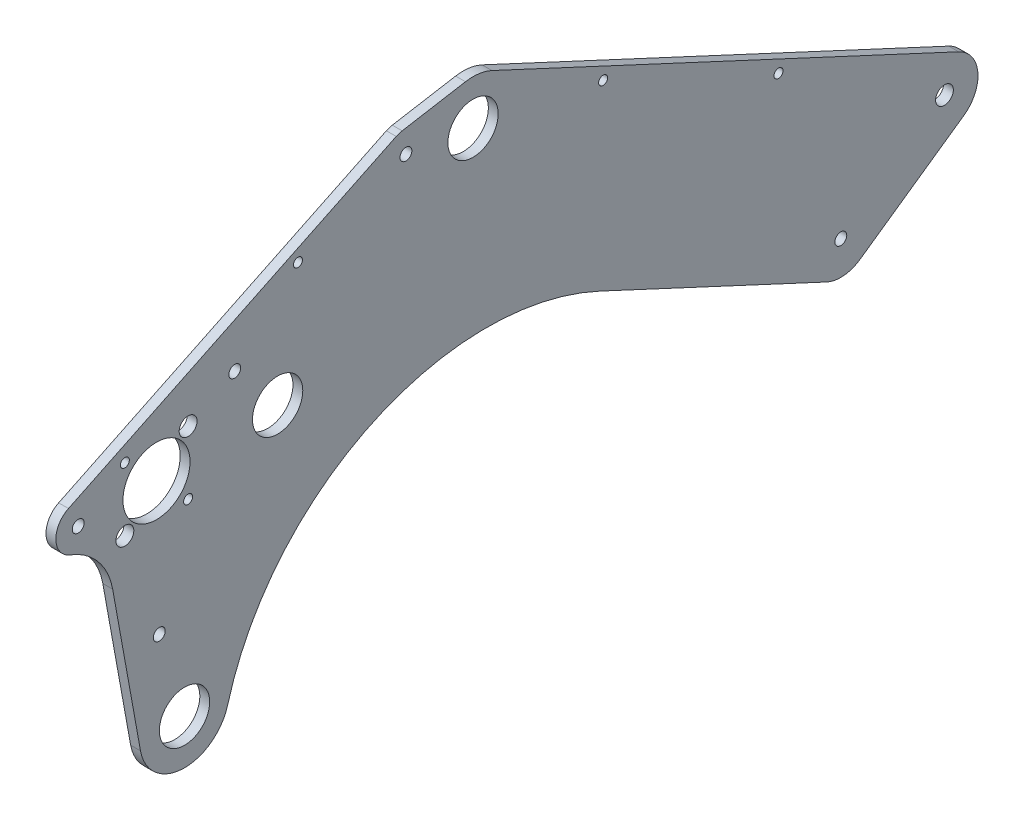
SolidWorks part; units mm, degrees
material "Acrylic (Medium-high impact)"
ref_plane "Front" through (0, 0, 0) normal (0, 0, 1) x (1, 0, 0)
ref_plane "Top" through (0, 0, 0) normal (0, 1, 0) x (1, 0, 0)
ref_plane "Right" through (0, 0, 0) normal (1, 0, 0) x (0, 0, -1)
sketch "Sketch1" plane through (0, 0, 0) normal (1, 0, 0) x (0, 0, -1)
  line L0 (-128.5875, -88.9) -> (-128.5875, -215.9)
  line L1 (-128.5875, -215.9) -> (-179.3875, -215.9)
  line L2 (-211.1375, -184.15) -> (-211.1375, -120.65)
  line L3 (-179.3875, -88.9) -> (-128.5875, -88.9)
  line L4 (-28.6872, -279.4) -> (-968.3377, -279.4) construction
  line L5 (-433.3875, -184.15) -> (-433.3875, -120.65) construction
  line L6 (-120.65, -76.2) -> (-95.25, -76.2)
  line L7 (-120.65, -76.2) -> (-120.65, -101.6)
  line L8 (-120.65, -101.6) -> (-95.25, -101.6)
  line L9 (-95.25, -76.2) -> (-95.25, -101.6)
  line L10 (-179.3875, 133.35) -> (-128.5875, 133.35) construction
  line L11 (-431.4942, -89.6952) -> (-179.3875, -120.65) construction
  line L12 (-378.637, 36.8798) -> (-179.3875, -120.65) construction
  line L13 (-267.6718, 117.5136) -> (-179.3875, -120.65) construction
  line L14 (-449.9497, -81.9883) -> (-397.0925, 44.5867)
  line L15 (-360.1816, 29.1728) -> (-413.0388, -97.4021)
  line L16 (-390.394, 53.0592) -> (-279.4287, 133.693)
  line L17 (-128.5875, -88.9) -> (-128.5875, 338.048) construction
  line L18 (-255.9148, 101.3341) -> (-366.8801, 20.7003)
  line L19 (-534.9875, 270.2474) -> (-534.9875, -123.3484) construction
  line L20 (-427.5738, 36.5062) -> (-411.6579, -87.1419)
  line L21 (-451.3306, -92.2485) -> (-467.2465, 31.3995)
  circle A0 centre (0, 0) radius 5.0419
  circle A1 centre (-431.4942, -89.6952) radius 11.557
  circle A2 centre (-378.637, 36.8798) radius 11.557
  circle A3 centre (-267.6718, 117.5136) radius 11.557
  arc A4 (-179.3875, -215.9) -> (-211.1375, -184.15) centre (-179.3875, -184.15) cw
  arc A5 (-211.1375, -120.65) -> (-179.3875, -88.9) centre (-179.3875, -120.65) cw
  circle A6 centre (-327.5258, -152.4) radius 120.65
  arc A7 (-433.3875, -120.65) -> (-179.3875, 133.35) centre (-179.3875, -120.65) cw construction
  circle A12 centre (-447.4102, 33.9528) radius 31.75
  arc A15 (-413.0388, -97.4021) -> (-449.9497, -81.9883) centre (-431.4942, -89.6952) cw
  arc A16 (-397.0925, 44.5867) -> (-360.1816, 29.1728) centre (-378.637, 36.8798) cw
  arc A17 (-366.8801, 20.7003) -> (-390.394, 53.0592) centre (-378.637, 36.8798) cw
  arc A18 (-279.4287, 133.693) -> (-255.9148, 101.3341) centre (-267.6718, 117.5136) cw
  arc A19 (-467.2465, 31.3995) -> (-427.5738, 36.5062) centre (-447.4102, 33.9528) cw
  arc A20 (-411.6579, -87.1419) -> (-451.3306, -92.2485) centre (-431.4942, -89.6952) cw
  point P45 (0, 0)
  point P46 (-451.0348, 27.3515)
  point P51 (0, 0)
  circle B0 centre (-267.6718, 117.5136) radius 20
  circle B1 centre (-378.637, 36.8798) radius 20
  circle B2 centre (-431.4942, -89.6952) radius 20
  circle B3 centre (-447.4102, 33.9528) radius 20
  dimension "D1" = 10.0838
  dimension "D2" = 23.114
  dimension "D4" = 31.75
  dimension "D10" = 241.3
  dimension "D19" = 63.5
  dimension "D26" = 89.6952
  dimension "D27" = 431.4942
  dimension "D3" = 127
  dimension "D5" = 82.55
  dimension "D6" = 190.5
  dimension "D7" = 25.4
  dimension "D8" = 7.9375
  dimension "D9" = 203.2
  dimension "D12" = 120.65
  dimension "D13" = 76.2
  dimension "D14" = 31.33
  dimension "D15" = 31.33
  dimension "D16" = 7
  dimension "D24" = 406.4
  dimension "D21" = 30
  dimension "D11" = 222.25
sketch_block_instance "Block1-1"
sketch_block "Block1" parameters "D1"=40
sketch_block_instance "Block2-1"
sketch_block "Block2"
sketch_block_instance "Block3-1"
sketch_block "Block3"
sketch_block_instance "Block4-1"
sketch_block "Block4" parameters "D1"=40
other "Belt1"
other "Belt2"
other "Belt4"
sketch "Sketch3" plane through (0, 0, 0) normal (1, 0, 0) x (0, 0, -1)
  line L0 (-431.4942, -89.6952) -> (0, 0) construction
  line L1 (0, 0) -> (-58.8496, -41.2069) construction
  line L2 (0, 0) -> (-89.6952, 431.4942) construction
  line L3 (0, 0) -> (-41.2069, 58.8496) construction
  line L4 (-58.8496, -41.2069) -> (-64.6229, -13.4332) construction
  line L5 (-41.2069, 58.8496) -> (-13.4332, 64.6229) construction
  line L6 (-41.2069, 58.8496) -> (-58.8496, -41.2069)
  line L7 (2.2602, 305.3637) -> (-41.2069, 58.8496)
  line L8 (0, 0) -> (117.5136, 267.6718) construction
  line L9 (0, 0) -> (-267.6718, 117.5136) construction
  line L10 (-267.6718, 117.5136) -> (-233.1688, -48.4691) construction
  line L11 (117.5136, 267.6718) -> (-48.4691, 233.1688) construction
  circle A0 centre (-89.6952, 431.4942) radius 25.4
  dimension "D1" = 50.8
  dimension "D2" = 90
  dimension "D3" = 101.6
  dimension "D4" = 250.317
  dimension "D5" = 80
sketch "Sketch2" plane through (0, 0, 0) normal (1, 0, 0) x (0, 0, -1)
  line L0 (-456.4885, -94.2169) -> (-472.3043, -6.7931)
  line L1 (-497.3852, 45.388) -> (-311.2968, 135.2988)
  line L2 (-431.4942, -89.6952) -> (-431.4942, 0) construction
  line L4 (8.035, 17.2726) -> (-256.9585, 140.5437)
  line L7 (-66.8845, -58.4795) -> (-195.7449, 1.4645)
  line L10 (-47.9229, -56.8118) -> (10.9266, -15.6048)
  line L11 (-307.9189, 136.3808) -> (-271.966, 142.5479)
  line L13 (-465.3707, 15.9923) -> (-429.4497, 51.9133) construction
  line L14 (-465.3707, 51.9133) -> (-429.4497, 15.9923) construction
  circle A0 centre (-267.6718, 117.5136) radius 14.2875
  circle A1 centre (-378.637, 36.8798) radius 14.2875
  circle A2 centre (-431.4942, -89.6952) radius 14.2875
  circle A3 centre (-447.4102, 33.9528) radius 19.05
  circle A9 centre (0, 0) radius 5.0419 construction
  circle A10 centre (0, 0) radius 5.0419
  arc A13 (-456.4885, -94.2169) -> (-406.9985, -96.4125) centre (-431.4942, -89.6952) ccw
  arc A16 (10.9266, -15.6048) -> (8.035, 17.2726) centre (0, 0) ccw
  arc A18 (-195.7449, 1.4645) -> (-406.9985, -96.4125) centre (-260.0245, -136.7162) ccw
  circle A19 centre (-58.8496, -41.2069) radius 3.3782
  circle A22 centre (-305.7718, 123.8636) radius 3.3782
  arc A23 (-311.2968, 135.2988) -> (-307.9189, 136.3808) centre (-305.7718, 123.8636) cw
  circle A24 centre (-267.6718, 117.5136) radius 25.4 construction
  circle A27 centre (-429.4497, 51.9133) radius 5.08
  circle A28 centre (-465.3707, 51.9133) radius 2.5527
  circle A29 centre (-465.3707, 15.9923) radius 5.08
  circle A30 centre (-429.4497, 15.9923) radius 2.5527
  circle A31 centre (-447.4102, 33.9528) radius 25.4 construction
  circle A32 centre (-491.8602, 33.9528) radius 3.3782
  arc A34 (-497.3852, 45.388) -> (-496.3441, 22.0707) centre (-491.8602, 33.9528) ccw
  arc A35 (-496.3441, 22.0707) -> (-472.3043, -6.7931) centre (-509.7957, -13.5757) cw
  circle A37 centre (-447.4102, 33.9528) radius 31.75 construction
  circle A38 centre (-491.8602, 33.9528) radius 7.9375 construction
  circle A39 centre (-445.8227, -42.2472) radius 3.3782
  circle A40 centre (-445.8227, -42.2472) radius 7.9375 construction
  circle A41 centre (-402.9602, 65.7028) radius 3.3782
  arc A42 (-66.8845, -58.4795) -> (-47.9229, -56.8118) centre (-58.8496, -41.2069) ccw
  arc A43 (-271.966, 142.5479) -> (-256.9585, 140.5437) centre (-267.6718, 117.5136) cw
  point P11 (-325.5172, 126.9125)
  point P25 (-314.4665, 140.2016)
  point P37 (-318.6042, 136.8162)
  dimension "D1" = 28.575
  dimension "D2" = 38.1
  dimension "D3" = 6.35
  dimension "D4" = 50.8
  dimension "D5" = 12.7
  dimension "D6" = 38.1
  dimension "D7" = 19.05
  dimension "D8" = 152.4
  dimension "D10" = 6.7564
  dimension "D11" = 6.7564
  dimension "D12" = 15.875
  dimension "D13" = 12.7
  dimension "D17" = 15.875
  dimension "D18" = 5.1054
  dimension "D19" = 10.16
  dimension "D20" = 50.8
  dimension "D21" = 25.4
  dimension "D22" = 38.1
  dimension "D23" = 1.5875
  dimension "D16" = 44.45
  dimension "D15" = 31.75
  dimension "D24" = 76.2
  dimension "D25" = 44.45
  dimension "D9" = 19.05
extrude "Boss-Extrude1" add sketch "Sketch2" along normal blind 5.588
sketch "Sketch4" plane through (5.588, 0, 0) normal (1, 0, 0) x (0, 0, -1)
  line L0 (-378.637, 36.8798) -> (-267.6718, 117.5136) construction
  line L1 (-311.2968, 135.2988) -> (-497.3852, 45.388) construction
  line L3 (-367.1038, 101.2826) -> (-458.5854, 57.0822) construction
  line L4 (-458.5854, 57.0822) -> (-447.4102, 33.9528) construction
  line L6 (8.035, 17.2726) -> (-256.9585, 140.5437) construction
  line L11 (-293.3872, 150.4864) -> (-193.8059, 104.1626) construction
  line L12 (-193.8059, 104.1626) -> (-94.2247, 57.8388) construction
  line L13 (-94.2247, 57.8388) -> (5.3566, 11.5151) construction
  line L14 (-293.3872, 150.4864) -> (-305.7718, 123.8636) construction
  line L15 (0, 0) -> (5.3566, 11.5151) construction
  circle A4 centre (-367.1038, 101.2826) radius 2.5527
  circle A5 centre (-193.8059, 104.1626) radius 2.5527
  circle A6 centre (-94.2247, 57.8388) radius 2.5527
  point P4 (-443.6188, 78.8209)
  point P6 (-387.262, 90.5963)
  dimension "D1" = 6.35
  dimension "D2" = 5.1054
  dimension "D3" = 101.6
  dimension "D6" = 6.35
extrude "Cut-Extrude1" cut sketch "Sketch4" against normal through all
